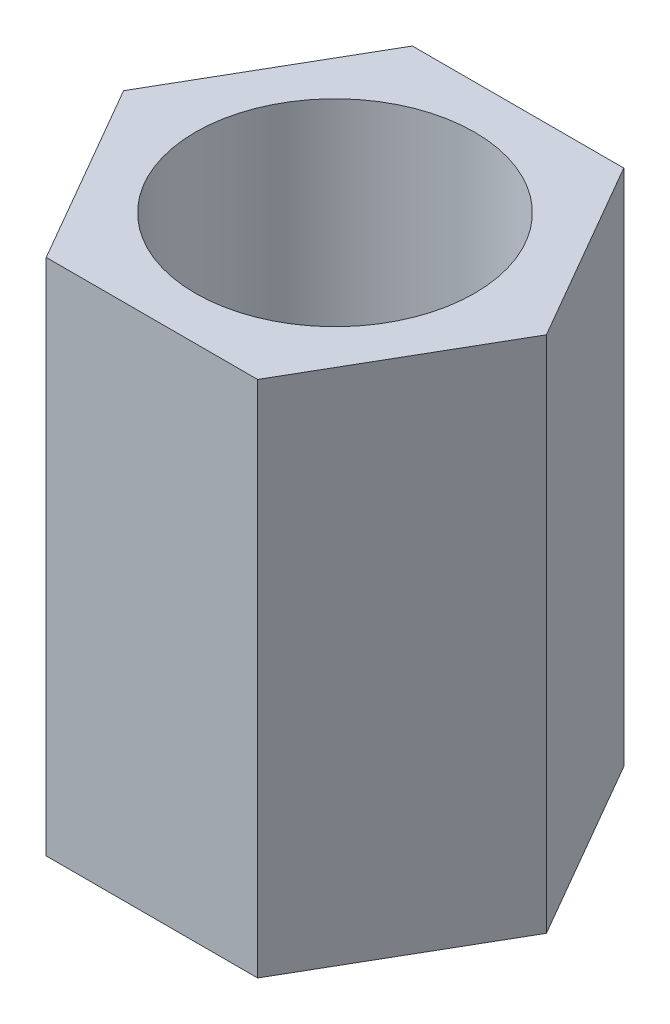
SolidWorks part; units mm, degrees
ref_plane "Front Plane" through (0, 0, 0) normal (0, 0, 1) x (1, 0, 0)
ref_plane "Top Plane" through (0, 0, 0) normal (0, 1, 0) x (1, 0, 0)
ref_plane "Right Plane" through (0, 0, 0) normal (1, 0, 0) x (0, 0, -1)
sketch "Sketch1" plane through (0, 0, 0) normal (0, 1, 0) x (1, 0, 0)
  line L1 (9.2376, 0) -> (4.6188, 8)
  line L2 (4.6188, 8) -> (-4.6188, 8)
  line L3 (-4.6188, 8) -> (-9.2376, 0)
  line L4 (-9.2376, 0) -> (-4.6188, -8)
  line L5 (-4.6188, -8) -> (4.6188, -8)
  line L6 (4.6188, -8) -> (9.2376, 0)
  circle A0 centre (0, 0) radius 8 construction
  circle A1 centre (0, 0) radius 4.1
  dimension "D1" = 16
  dimension "D2" = 8.2
extrude "Boss-Extrude1" add sketch "Sketch1" along normal blind 22.65
sketch "Sketch2" plane through (0, 22.65, 0) normal (0, 1, 0) x (1, 0, 0)
  circle A0 centre (0, 0) radius 6.1
  dimension "D1" = 12.2
extrude "Cut-Extrude1" cut sketch "Sketch2" against normal blind 20
